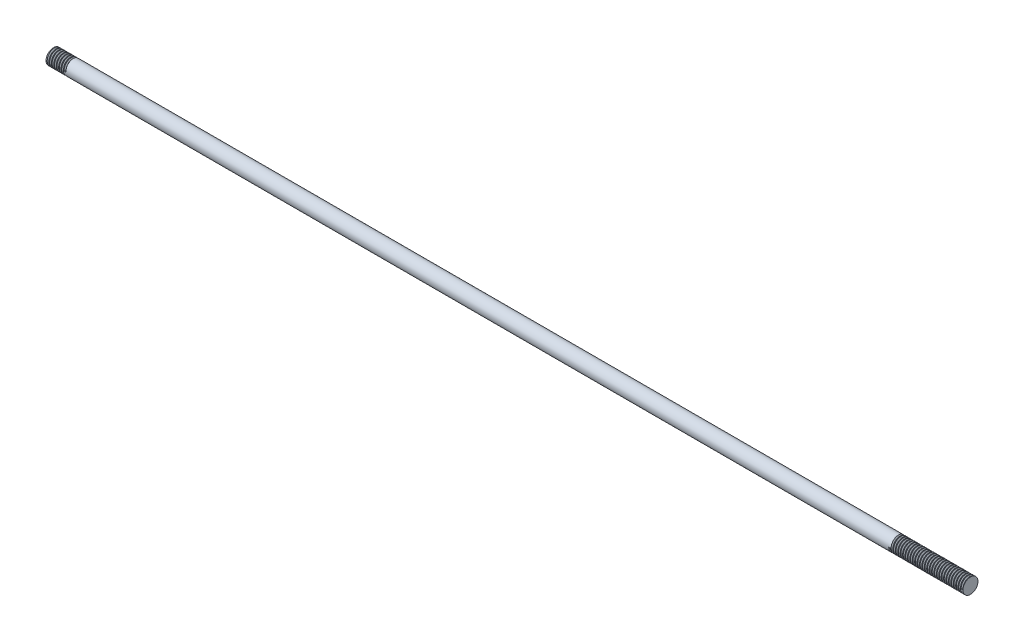
SolidWorks part; units mm, degrees
material "Stainless Steel (ferritic)"
ref_plane "Front Plane" through (0, 0, 0) normal (0, 0, 1) x (1, 0, 0)
ref_plane "Top Plane" through (0, 0, 0) normal (0, 1, 0) x (1, 0, 0)
ref_plane "Right Plane" through (0, 0, 0) normal (1, 0, 0) x (0, 0, -1)
sketch "Sketch1" plane through (0, 0, 0) normal (1, 0, 0) x (0, 0, -1)
  circle A0 centre (0, 0) radius 2.5
  dimension "D1" = 5
extrude "Boss-Extrude1" add sketch "Sketch1" along normal blind 304
thread "Thread1" pitch 0.8 method cut profile "Thread Profile1" start angle 0, offset 0, length 24, pitch 0.8, diameter 5
ref_plane "Plane1" through (304, 0, 2.5) normal (0, -1, 0) x (0, 0, 1)
sketch "Thread Profile1" plane through (304, 0, 2.5) normal (0, -1, 0) x (0, 0, 1)
  line L0 (0, 0) -> (0, 0.8) construction
  line L1 (0, 0.6) -> (-0.433, 0.35)
  line L2 (-0.433, 0.35) -> (-0.433, 0.25)
  line L3 (-0.433, 0.25) -> (0, 0)
  line L4 (-0.433, 0.3) -> (0, 0.3) construction
  line L11 (0, 0.6) -> (0, 0)
  point P6 (0, 0)
  dimension "Pitch" = 0.8
  dimension "Profile_Angle" = 60
  dimension "Profile_Land" = 0.1
  dimension "Profile_Height" = 0.433
thread "Thread2" pitch 0.8 method cut profile "Thread Profile2" start angle 0, offset 0, length 6, pitch 0.8, diameter 5
ref_plane "Plane2" through (0, 0, -2.5) normal (0, -1, 0) x (0, 0, -1)
sketch "Thread Profile2" plane through (0, 0, -2.5) normal (0, -1, 0) x (0, 0, -1)
  line L0 (0, 0) -> (0, 0.8) construction
  line L1 (0, 0.6) -> (-0.433, 0.35)
  line L2 (-0.433, 0.35) -> (-0.433, 0.25)
  line L3 (-0.433, 0.25) -> (0, 0)
  line L4 (-0.433, 0.3) -> (0, 0.3) construction
  line L11 (0, 0.6) -> (0, 0)
  point P6 (0, 0)
  dimension "Pitch" = 0.8
  dimension "Profile_Angle" = 60
  dimension "Profile_Land" = 0.1
  dimension "Profile_Height" = 0.433
